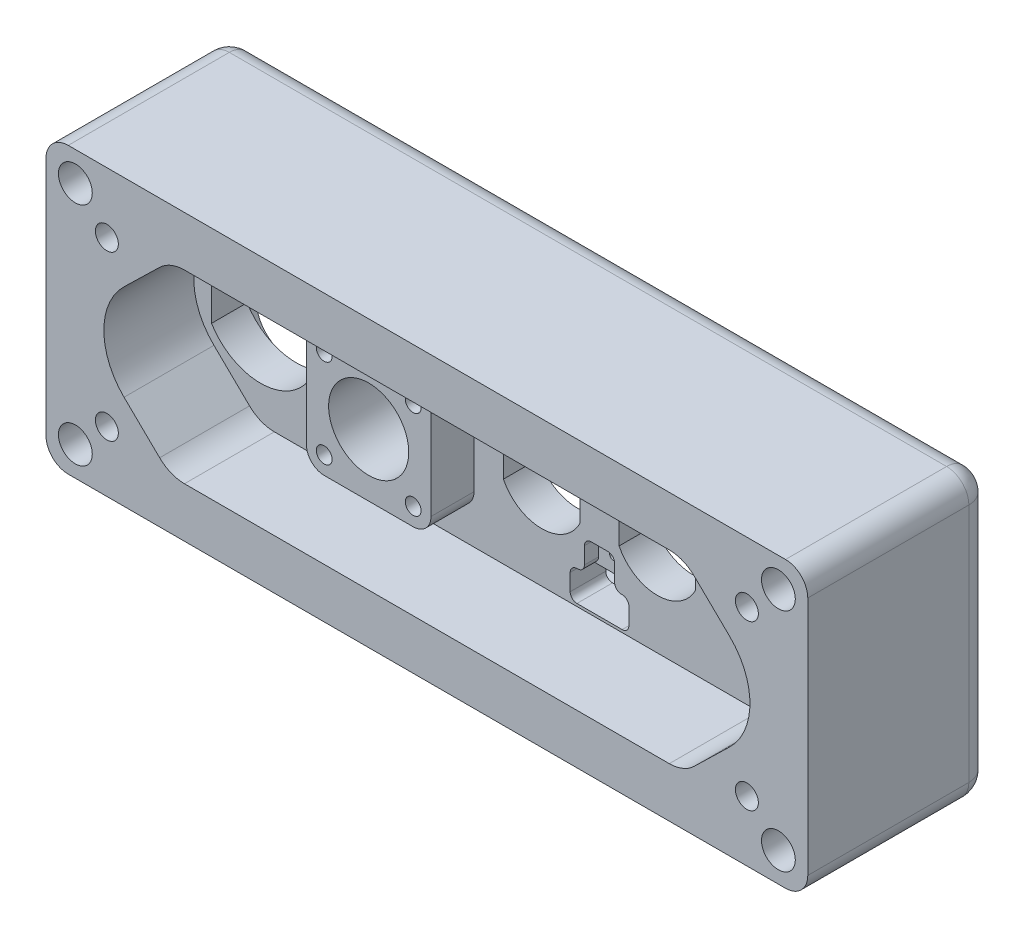
SolidWorks part; units mm, degrees
ref_plane "Front Plane" through (0, 0, 0) normal (0, 0, 1) x (1, 0, 0)
ref_plane "Top Plane" through (0, 0, 0) normal (0, 1, 0) x (1, 0, 0)
ref_plane "Right Plane" through (0, 0, 0) normal (1, 0, 0) x (0, 0, -1)
sketch "Sketch1" plane through (0, 0, 0) normal (0, 0, 1) x (1, 0, 0)
  line L1 (-54.356, -20.32) -> (54.356, -20.32)
  line L2 (-54.356, -20.32) -> (-54.356, 20.32)
  line L3 (-54.356, 20.32) -> (54.356, 20.32)
  line L4 (54.356, -20.32) -> (54.356, 20.32)
  line L5 (-54.356, -20.32) -> (54.356, 20.32) construction
  line L6 (-54.356, 20.32) -> (54.356, -20.32) construction
  point P0 (0, 0)
  dimension "D1" = 108.712
  dimension "D2" = 40.64
extrude "Boss-Extrude1" add sketch "Sketch1" along normal blind 26.162
sketch "Sketch2" plane through (0, 0, 26.162) normal (0, 0, 1) x (1, 0, 0)
  line L0 (0, 29.2967) -> (0, -34.4423) construction
  line L1 (-70.3785, 0) -> (64.403, 0) construction
  line L2 (54.356, 20.32) -> (-54.356, 20.32) construction
  line L3 (-43.2173, -6.8278) -> (-38.1368, -11.7695)
  line L4 (-54.356, 20.32) -> (-54.356, -20.32) construction
  line L5 (-34.5948, -13.208) -> (34.5948, -13.208)
  line L6 (-34.5948, 13.208) -> (34.5948, 13.208)
  line L7 (-43.2173, 6.8278) -> (-38.1368, 11.7695)
  line L8 (43.2173, 6.8278) -> (38.1368, 11.7695)
  line L9 (43.2173, -6.8278) -> (38.1368, -11.7695)
  arc A0 (-43.2173, 6.8278) -> (-43.2173, -6.8278) centre (-36.576, 0) ccw
  arc A1 (-38.1368, -11.7695) -> (-34.5948, -13.208) centre (-34.5948, -8.128) ccw
  arc A2 (-38.1368, 11.7695) -> (-34.5948, 13.208) centre (-34.5948, 8.128) cw
  arc A3 (38.1368, 11.7695) -> (34.5948, 13.208) centre (34.5948, 8.128) ccw
  arc A4 (43.2173, 6.8278) -> (43.2173, -6.8278) centre (36.576, 0) cw
  arc A5 (38.1368, -11.7695) -> (34.5948, -13.208) centre (34.5948, -8.128) cw
  point P6 (0, 13.208)
  point P29 (0, -13.208)
  dimension "D1" = 19.05
  dimension "D3" = 10.16
  dimension "D2" = 28.448
  dimension "D4" = 17.78
  dimension "D5" = 19.7612
extrude "Cut-Extrude1" cut sketch "Sketch2" against normal blind 12.827
sketch "Sketch3" plane through (0, 0, 13.335) normal (0, 0, 1) x (1, 0, 0)
  line L0 (-43.561, 4.2791) -> (-43.561, -4.2791)
  line L1 (-29.591, 4.2791) -> (-29.591, -4.2791)
  line L2 (-1.905, 2.709) -> (-1.905, -2.709)
  line L3 (9.017, 2.709) -> (9.017, -2.709)
  line L4 (-54.356, 20.32) -> (-54.356, -20.32) construction
  line L5 (-36.576, 0) -> (-36.576, -8.1915) construction
  line L6 (54.356, -20.32) -> (54.356, 20.32) construction
  line L7 (3.556, 0) -> (3.556, 6.096) construction
  arc A0 (-29.591, 4.2791) -> (-43.561, 4.2791) centre (-36.576, 0) ccw
  arc A1 (9.017, 2.709) -> (-1.905, 2.709) centre (3.556, 0) ccw
  arc A2 (-43.561, -4.2791) -> (-29.591, -4.2791) centre (-36.576, 0) ccw
  arc A3 (-1.905, -2.709) -> (9.017, -2.709) centre (3.556, 0) ccw
  circle A4 centre (-14.986, 0) radius 5.715
  point P18 (0, 0)
  dimension "D1" = 16.383
  dimension "D4" = 12.192
  dimension "D8" = 11.43
  dimension "D2" = 17.78
  dimension "D3" = 13.97
  dimension "D5" = 50.8
  dimension "D6" = 10.922
  dimension "D7" = 39.37
extrude "Cut-Extrude3" cut sketch "Sketch3" against normal through all contours L0 A2 L1 A0 | A4 region at (-36.576, 0, 13.335) region at (-14.986, 0, 13.335)
extrude "Cut-Extrude4" cut sketch "Sketch3<4>" against normal through all contours L2 A3 L3 A1 region at (3.556, 0, 13.335)
sketch "Sketch3<4>" plane through (0, 0, 13.335) normal (0, 0, 1) x (1, 0, 0) same geometry as "Sketch3"
pattern_linear "LPattern1" count 3 spacing 16.51 along (1, 0, 0) of "Cut-Extrude4"
hole_wizard "1/4 (0.25) Diameter Hole1" positions "Sketch6" profile "Sketch7" hole size "1/4" standard "ANSI Inch"
sketch "Sketch6" plane through (0, 0, 26.162) normal (0, 0, 1) x (1, 0, 0)
  line L0 (-54.356, 0) -> (54.356, 0) construction
  line L1 (-54.356, 20.32) -> (-54.356, -20.32) construction
  line L2 (54.356, -20.32) -> (54.356, 20.32) construction
  line L4 (0, 20.32) -> (0, -20.32) construction
  line L5 (54.356, 20.32) -> (-54.356, 20.32) construction
  line L6 (-54.356, -20.32) -> (54.356, -20.32) construction
  point P0 (-50.165, 16.129)
  point P2 (-50.165, -16.129)
  point P4 (50.165, -16.129)
  point P6 (50.165, 16.129)
  point P29 (-51.3977, 20.32)
  dimension "D1" = 4.191
  dimension "D2" = 4.191
sketch "Sketch7" plane through (-50.165, 16.129, 26.162) normal (1, 0, 0) x (0, -1, 0)
  line L0 (0, 0) -> (0, 5.2599)
  line L1 (0, 5.2599) -> (2.413, 3.81)
  line L2 (2.413, 3.81) -> (2.413, 0)
  line L5 (2.413, 0) -> (0, 0)
  line L10 (0, 5.2599) -> (-2.413, 3.81) construction
  line L11 (0, -6.35) -> (0, 107.95) construction
  dimension "Hole Dia." = 4.826
  dimension "Hole Depth" = 3.81
  dimension "Drill Angle" = 118
sketch "Sketch8" plane through (0, 0, 0) normal (0, 0, -1) x (-1, 0, 0)
  line L0 (54.356, -20.32) -> (-54.356, -20.32) construction
  line L1 (-45.466, -16.51) -> (45.466, -16.51)
  line L2 (-50.546, -11.43) -> (-50.546, 11.43)
  line L3 (-45.466, 16.51) -> (45.466, 16.51)
  line L4 (50.546, -11.43) -> (50.546, 11.43)
  line L5 (-50.546, -16.51) -> (50.546, 16.51) construction
  line L6 (-50.546, 16.51) -> (50.546, -16.51) construction
  line L7 (-54.356, -20.32) -> (-54.356, 20.32) construction
  arc A0 (45.466, 16.51) -> (50.546, 11.43) centre (45.466, 11.43) cw
  arc A1 (45.466, -16.51) -> (50.546, -11.43) centre (45.466, -11.43) ccw
  arc A2 (-45.466, -16.51) -> (-50.546, -11.43) centre (-45.466, -11.43) cw
  arc A3 (-50.546, 11.43) -> (-45.466, 16.51) centre (-45.466, 11.43) cw
  point P0 (0, 0)
  dimension "D1" = 5.08
  dimension "D2" = 3.81
  dimension "D3" = 3.81
extrude "Cut-Extrude5" cut sketch "Sketch8" against normal blind 8.255
hole_wizard "CBORE for 1/4 Binding Head Machine Screw1" positions "Sketch9" profile "Sketch10" counterbore size "1/4" standard "ANSI Inch" end condition through all
sketch "Sketch9" plane through (0, 0, 8.255) normal (0, 0, -1) x (-1, 0, 0)
  line L0 (0, 20.32) -> (0, -20.32) construction
  line L1 (-54.356, 20.32) -> (54.356, 20.32) construction
  line L2 (54.356, -20.32) -> (-54.356, -20.32) construction
  line L4 (-54.356, -20.32) -> (-54.356, 20.32) construction
  line L5 (-54.356, 0) -> (54.356, 0) construction
  line L6 (54.356, 20.32) -> (54.356, -20.32) construction
  point P0 (-45.6692, 11.684)
  point P2 (-45.6692, -11.684)
  point P4 (45.6692, -11.684)
  point P6 (45.6692, 11.684)
  dimension "D1" = 8.6868
  dimension "D2" = 8.636
sketch "Sketch10" plane through (45.6692, 11.684, 8.255) normal (1, 0, 0) x (0, 1, 0)
  line L0 (0, 0) -> (0, 17.907)
  line L1 (0, 17.907) -> (1.6383, 17.907)
  line L3 (1.6383, 17.907) -> (1.6383, 2.8448)
  line L4 (1.6383, 2.8448) -> (2.7813, 2.8448)
  line L5 (2.7813, 2.8448) -> (2.7813, 0)
  line L7 (2.7813, 0) -> (0, 0)
  line L11 (0, -6.35) -> (0, 107.95) construction
  dimension "Thru Hole Dia." = 3.2766
  dimension "Thru Hole Depth" = 17.907
  dimension "C'Bore Dia." = 5.5626
  dimension "C'Bore Depth" = 2.8448
sketch "Sketch12" plane through (0, 0, 13.335) normal (0, 0, 1) x (1, 0, 0)
  line L0 (14.9352, -8.509) -> (15.0368, -8.509)
  line L1 (8.5852, -12.827) -> (15.0368, -12.827)
  line L2 (7.62, -11.8618) -> (7.62, -9.4742)
  line L3 (8.5852, -8.509) -> (8.6868, -8.509)
  line L4 (16.002, -11.8618) -> (16.002, -9.4742)
  line L5 (7.62, -12.827) -> (16.002, -8.509) construction
  line L6 (7.62, -8.509) -> (16.002, -12.827) construction
  line L7 (10.6172, -4.191) -> (13.0048, -4.191)
  line L8 (9.652, -5.1562) -> (9.652, -7.5438)
  line L10 (13.97, -5.1562) -> (13.97, -7.5438)
  line L11 (9.652, -4.191) -> (13.97, -8.509) construction
  line L12 (9.652, -8.509) -> (13.97, -4.191) construction
  line L13 (8.6868, -8.509) -> (14.9352, -8.509)
  line L14 (54.356, 20.32) -> (-54.356, 20.32) construction
  line L16 (-54.356, 20.32) -> (-54.356, -20.32) construction
  arc A0 (10.6172, -4.191) -> (9.652, -5.1562) centre (10.6172, -5.1562) ccw
  arc A1 (13.0048, -4.191) -> (13.97, -5.1562) centre (13.0048, -5.1562) cw
  arc A2 (14.9352, -8.509) -> (13.97, -7.5438) centre (14.9352, -7.5438) cw
  arc A3 (15.0368, -8.509) -> (16.002, -9.4742) centre (15.0368, -9.4742) cw
  arc A4 (15.0368, -12.827) -> (16.002, -11.8618) centre (15.0368, -11.8618) ccw
  arc A5 (8.5852, -12.827) -> (7.62, -11.8618) centre (8.5852, -11.8618) cw
  arc A6 (7.62, -9.4742) -> (8.5852, -8.509) centre (8.5852, -9.4742) cw
  arc A7 (9.652, -7.5438) -> (8.6868, -8.509) centre (8.6868, -7.5438) cw
  circle A8 centre (11.811, -6.35) radius 0.7323
  point P0 (11.811, -10.668)
  point P5 (11.811, -6.35)
  dimension "D5" = 0.9652
  dimension "D1" = 4.318
  dimension "D2" = 4.318
  dimension "D3" = 8.382
  dimension "D4" = 4.318
  dimension "D6" = 26.67
  dimension "D7" = 66.167
extrude "Cut-Extrude6" cut sketch "Sketch12" against normal through all contours A6 L2 A5 L1 A4 L4 A3 L0 L13 L3 region at (11.811, -10.668, 13.335)
extrude "Cut-Extrude7" cut sketch "Sketch12<3>" against normal blind 2.032 contours L8 A7 L13 A2 L10 A1 L7 A0 A8 | A8 region at (11.811, -8.433, 13.335) region at (11.811, -6.35, 13.335)
sketch "Sketch12<3>" plane through (0, 0, 13.335) normal (0, 0, 1) x (1, 0, 0) same geometry as "Sketch12"
hole_wizard "#0-80 Tapped Hole1" positions "Sketch15" profile "Sketch16" tap size "#0-80" standard "ANSI Inch"
sketch "Sketch15" plane through (0, 0, 11.303) normal (0, 0, 1) x (1, 0, 0)
  line L0 (-54.356, 20.32) -> (-54.356, -20.32) construction
  line L1 (54.356, 20.32) -> (-54.356, 20.32) construction
  point P0 (11.811, -6.35)
  dimension "D1" = 66.167
  dimension "D2" = 26.67
sketch "Sketch16" plane through (11.811, -6.35, 11.303) normal (1, 0, 0) x (0, -1, 0)
  line L0 (0, 0) -> (0, 1.8819)
  line L1 (0, 1.8819) -> (0.5956, 1.524)
  line L2 (0.5956, 1.524) -> (0.5956, 0)
  line L5 (0.5956, 0) -> (0, 0)
  line L10 (0, 1.8819) -> (-0.5956, 1.524) construction
  line L11 (0, -6.35) -> (0, 107.95) construction
  dimension "Tap Drill Dia." = 1.1913
  dimension "Tap Drill Depth" = 1.524
  dimension "Drill Angle" = 118
cosmetic thread "Hole Thread1" parameters "D1"=1.524, "D2"=1.524
sketch "Sketch17" plane through (0, 0, 13.335) normal (0, 0, 1) x (1, 0, 0)
  line L1 (-21.336, -8.89) -> (-8.636, -8.89)
  line L2 (-23.876, -6.35) -> (-23.876, 6.35)
  line L3 (-21.336, 8.89) -> (-8.636, 8.89)
  line L4 (-6.096, -6.35) -> (-6.096, 6.35)
  line L5 (-23.876, -8.89) -> (-6.096, 8.89) construction
  line L6 (-23.876, 8.89) -> (-6.096, -8.89) construction
  arc A0 (-8.636, -8.89) -> (-6.096, -6.35) centre (-8.636, -6.35) ccw
  arc A1 (-8.636, 8.89) -> (-6.096, 6.35) centre (-8.636, 6.35) cw
  arc A2 (-23.876, 6.35) -> (-21.336, 8.89) centre (-21.336, 6.35) cw
  arc A3 (-21.336, -8.89) -> (-23.876, -6.35) centre (-21.336, -6.35) cw
  circle A4 centre (-14.986, 0) radius 5.715 construction
  circle A5 centre (-14.986, 0) radius 5.715
  point P0 (-14.986, 0)
  dimension "D3" = 2.54
  dimension "D1" = 17.78
  dimension "D2" = 17.78
extrude "Boss-Extrude2" add sketch "Sketch17" along normal blind 6.1468
hole_wizard "#4-40 Tapped Hole4" positions "Sketch20" profile "Sketch21" tap size "#4-40" standard "ANSI Inch"
sketch "Sketch20" plane through (0, 0, 19.4818) normal (0, 0, 1) x (1, 0, 0)
  point P0 (-21.336, 6.35)
  point P3 (-8.636, 6.35)
  point P6 (-8.636, -6.35)
  point P9 (-21.336, -6.35)
sketch "Sketch21" plane through (-21.336, 6.35, 19.4818) normal (1, 0, 0) x (0, -1, 0)
  line L0 (0, 0) -> (0, 3.7272)
  line L1 (0, 3.7272) -> (1.1303, 3.048)
  line L2 (1.1303, 3.048) -> (1.1303, 0)
  line L5 (1.1303, 0) -> (0, 0)
  line L10 (0, 3.7272) -> (-1.1303, 3.048) construction
  line L11 (0, -6.35) -> (0, 107.95) construction
  dimension "Tap Drill Dia." = 2.2606
  dimension "Tap Drill Depth" = 3.048
  dimension "Drill Angle" = 118
cosmetic thread "Hole Thread2" parameters "D1"=3.048, "D2"=2.8448
cosmetic thread "Hole Thread3" parameters "D1"=3.048, "D2"=2.8448
cosmetic thread "Hole Thread4" parameters "D1"=3.048, "D2"=2.8448
cosmetic thread "Hole Thread5" parameters "D1"=3.048, "D2"=2.8448
sketch "Sketch22" plane through (0, 0, 8.255) normal (0, 0, -1) x (-1, 0, 0)
  line L0 (-54.356, 20.32) -> (54.356, 20.32) construction
  line L1 (-41.0464, 8.5852) -> (1.1684, 8.5852)
  line L2 (-42.672, 10.2108) -> (-42.672, 13.0048)
  line L3 (-41.0464, 14.6304) -> (1.1684, 14.6304)
  line L4 (2.794, 10.2108) -> (2.794, 13.0048)
  line L5 (-54.356, -20.32) -> (-54.356, 20.32) construction
  arc A0 (1.1684, 8.5852) -> (2.794, 10.2108) centre (1.1684, 10.2108) ccw
  arc A1 (1.1684, 14.6304) -> (2.794, 13.0048) centre (1.1684, 13.0048) cw
  arc A2 (-41.0464, 8.5852) -> (-42.672, 10.2108) centre (-41.0464, 10.2108) cw
  arc A3 (-42.672, 13.0048) -> (-41.0464, 14.6304) centre (-41.0464, 13.0048) cw
  dimension "D5" = 1.6256
  dimension "D1" = 5.6896
  dimension "D2" = 11.7348
  dimension "D3" = 11.684
  dimension "D4" = 57.15
extrude "Cut-Extrude8" cut sketch "Sketch22" against normal blind 1.27
sketch "Sketch23" plane through (0, 0, 9.525) normal (0, 0, -1) x (-1, 0, 0)
  text T0 "PWR     AUD1   AUD2"
extrude "Boss-Extrude3" add sketch "Sketch23" along normal blind 0.508
fillet "Fillet1" radius 3.175 8 edges at (-54.356, 0, 0) (0, -20.32, 0) (54.356, 0, 0) (0, 20.32, 0) (-54.356, 20.32, 13.081) (-54.356, -20.32, 13.081) (54.356, -20.32, 13.081) (54.356, 20.32, 13.081)
